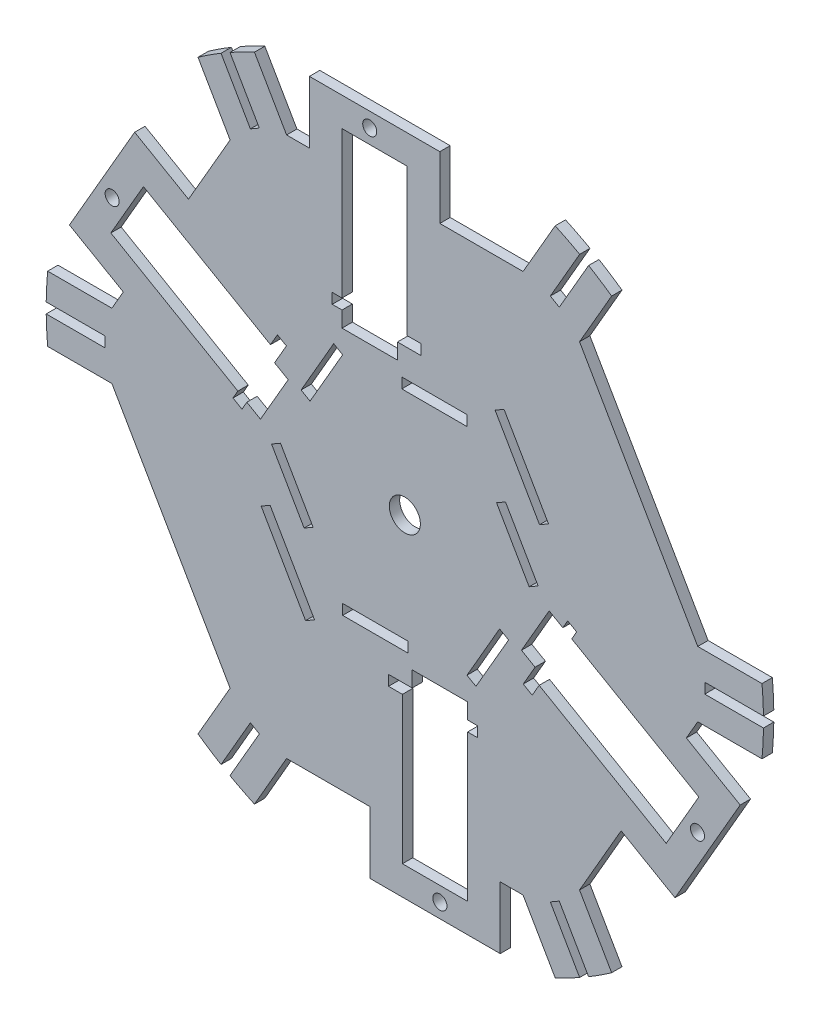
SolidWorks part; units mm, degrees
note: '?' marks a value the reader was unsure of.
ref_plane "Front Plane" through (0, 0, 0) normal (0, 0, 1) x (1, 0, 0)
ref_plane "Top Plane" through (0, 0, 0) normal (0, 1, 0) x (1, 0, 0)
ref_plane "Right Plane" through (0, 0, 0) normal (1, 0, 0) x (0, 0, -1)
sketch "Sketch1" plane through (0, 0, 0) normal (0, 0, 1) x (1, 0, 0)
  line L0 (-4.7625, 0) -> (-4.7625, 42.8001) construction
  line L1 (-4.7625, 40) -> (-2.2625, 40)
  line L2 (-2.2625, 40) -> (-2.2625, 48)
  line L3 (-2.2625, 48) -> (0.7375, 48)
  line L4 (0.7375, 48) -> (0.7375, 93)
  line L5 (0.7375, 93) -> (-19.2625, 93)
  line L6 (-19.2625, 93) -> (-19.2625, 40)
  line L7 (-19.2625, 40) -> (-16.7625, 40)
  line L8 (-16.7625, 40) -> (-4.7625, 40)
  line L9 (-4.7625, 40) -> (-4.7625, 0)
  line L10 (4.7625, -40) -> (2.2625, -40)
  line L11 (2.2625, -40) -> (2.2625, -48)
  line L12 (2.2625, -48) -> (-0.7375, -48)
  line L13 (-0.7375, -48) -> (-0.7375, -93)
  line L14 (-0.7375, -93) -> (19.2625, -93)
  line L15 (19.2625, -93) -> (19.2625, -40)
  line L16 (19.2625, -40) -> (16.7625, -40)
  line L17 (16.7625, -40) -> (4.7625, -40)
  line L18 (-2.2625, 40) -> (2.2625, -40) construction
  line L19 (37.0223, -15.8756) -> (35.7723, -18.0406)
  line L20 (35.7723, -18.0406) -> (42.7005, -22.0406)
  line L21 (42.7005, -22.0406) -> (41.2005, -24.6387)
  line L22 (41.2005, -24.6387) -> (80.1716, -47.1387)
  line L23 (80.1716, -47.1387) -> (90.1716, -29.8182)
  line L24 (90.1716, -29.8182) -> (44.2723, -3.3182)
  line L25 (44.2723, -3.3182) -> (43.0223, -5.4832)
  line L26 (43.0223, -5.4832) -> (37.0223, -15.8756)
  line L27 (0, 0) -> (2.2625, -40) construction
  line L28 (0, 0) -> (35.7723, -18.0406) construction
  line L29 (-37.0223, 15.8756) -> (-35.7723, 18.0406)
  line L30 (-35.7723, 18.0406) -> (-42.7005, 22.0406)
  line L31 (-42.7005, 22.0406) -> (-41.2005, 24.6387)
  line L32 (-41.2005, 24.6387) -> (-80.1716, 47.1387)
  line L33 (-80.1716, 47.1387) -> (-90.1716, 29.8182)
  line L34 (-90.1716, 29.8182) -> (-44.2723, 3.3182)
  line L35 (-44.2723, 3.3182) -> (-43.0223, 5.4832)
  line L36 (-43.0223, 5.4832) -> (-37.0223, 15.8756)
  line L37 (-35.7723, 18.0406) -> (0, 0) construction
  circle A0 centre (0, 0) radius 110
  circle A1 centre (0, 0) radius 4.7625
  point P14 (-4.7625, 0)
  point P27 (0, 0)
  point P46 (0, 0)
  dimension "D5" = 9.525
  dimension "D11" = 220
  dimension "D1" = 17
  dimension "D2" = 12
  dimension "D3" = 53
  dimension "D4" = 45
  dimension "D6" = 20
  dimension "D7" = 40
  dimension "D10" = 60
  dimension "D8" = 2
  dimension "D9" = 2
  dimension "D12" = 2
extrude "Boss-Extrude1" add sketch "Sketch1" along normal mid plane 3.175
sketch "Sketch2" plane through (0, 0, 1.5875) normal (0, 0, 1) x (1, 0, 0)
  line L0 (-0.7375, -93) -> (19.2625, -93) construction
  line L1 (-10.7375, -82.8085) -> (-10.7375, -101.88)
  line L2 (0, 0) -> (45.6639, 0) construction
  line L3 (29.2625, -101.88) -> (29.2625, -82.8085)
  line L4 (-36.2625, -82.8085) -> (-10.7375, -82.8085)
  line L5 (-10.7375, -101.88) -> (9.2625, -101.88)
  line L6 (10.7625, -99.5925) -> (10.7625, -101.88) construction
  line L7 (9.2625, -101.88) -> (29.2625, -101.88)
  line L8 (29.2625, -82.8085) -> (36.2625, -82.8085)
  line L9 (9.2625, -93) -> (9.2625, -101.88) construction
  line L11 (10.7625, -40) -> (10.7625, -97.4387) construction
  line L12 (0, -53.2538) -> (0, -302.3208) construction
  line L13 (0, -55) -> (0, 55) construction
  line L14 (0, 0) -> (55, -95.2628) construction
  line L15 (0, 0) -> (-55, -95.2628) construction
  line L16 (19.2625, -40) -> (2.2625, -40) construction
  line L19 (-36.2625, -82.8085) -> (-46.112, -99.8683)
  line L24 (36.2625, -82.8085) -> (46.112, -99.8683)
  arc A0 (-46.112, -99.8683) -> (46.112, -99.8683) centre (0, 0) ccw
  circle A1 centre (0, 0) radius 110 construction
  circle A2 centre (0, 0) radius 110 construction
  circle A3 centre (10.7625, -97.4387) radius 2.1538
  point P4 (10.7625, -95.285)
  dimension "D10" = 4.3075
  dimension "D2" = 2.2875
  dimension "D3" = 60
  dimension "D4" = 10
  dimension "D5" = 7
  dimension "D6" = 2.285
  dimension "D7" = 20
  dimension "D9" = 10
extrude "Cut-Extrude3" cut sketch "Sketch2" against normal through all
ref_axis "Axis1" through (0, 0, 1.7463) along (0, 0, -1)?
pattern_circular "CirPattern1" count 2 over 360 about axis through (0, 0, 0) along (0, 0, 1) of "Cut-Extrude3"
pattern_circular "CirPattern2" count 2 every 60 about axis through (0, 0, 0) along (0, 0, 1) of "CirPattern1", "Cut-Extrude3"
sketch "Sketch5" plane through (0, 0, 1.5875) normal (0, 0, 1) x (1, 0, 0)
  line L0 (0, 0) -> (-174.8424, -100.9453) construction
  line L1 (0, 0) -> (-55, -95.2628) construction
  line L2 (0, 0) -> (-151.9227, 0) construction
  line L3 (89.8455, 10) -> (53.583, 72.8085)
  line L4 (63.4325, 89.8683) -> (53.583, 72.8085)
  line L5 (-89.8455, -10) -> (-53.583, -72.8085)
  line L6 (-36.2625, -82.8085) -> (-46.112, -99.8683) construction
  line L7 (109.5445, 10) -> (89.8455, 10)
  line L9 (-109.5445, 10) -> (-89.8455, 10) construction
  line L12 (-63.4325, -89.8683) -> (-53.583, -72.8085)
  line L13 (-109.5445, -10) -> (-89.8455, -10)
  arc A0 (-109.5445, -10) -> (-63.4325, -89.8683) centre (0, 0) ccw
  arc A1 (-109.5445, 10) -> (-46.112, -99.8683) centre (0, 0) ccw construction
  arc A2 (109.5445, 10) -> (63.4325, 89.8683) centre (0, 0) ccw
  point P19 (0, 0)
  point P23 (0, 0)
  point P26 (0, 0)
  dimension "D1" = 10
  dimension "D2" = 2
extrude "Cut-Extrude5" cut sketch "Sketch5" against normal through all
sketch "Sketch10" plane through (0, 0, 1.5875) normal (0, 0, 1) x (1, 0, 0)
  line L0 (-55.0026, -95.2673) -> (-50.5318, -87.5237) construction
  line L1 (-65.3691, -110.0476) -> (-56.3691, -94.4591)
  line L2 (-56.3691, -94.4591) -> (-47.3691, -78.8707)
  line L3 (-47.3691, -78.8707) -> (-44.6195, -80.4582)
  line L4 (-44.6195, -80.4582) -> (-53.6195, -96.0466)
  line L5 (-53.6195, -96.0466) -> (-62.6195, -111.6351)
  line L6 (-62.6195, -111.6351) -> (-65.3691, -110.0476)
  line L7 (-53.583, -72.8085) -> (-36.2625, -82.8085) construction
  line L8 (-89.8455, 10) -> (-89.8455, -10) construction
  line L9 (-127.9885, 1.5875) -> (-109.9885, 1.5875)
  line L10 (-109.9885, 1.5875) -> (-91.9885, 1.5875)
  line L11 (-91.9885, 1.5875) -> (-91.9885, -1.5875)
  line L12 (-91.9885, -1.5875) -> (-109.9885, -1.5875)
  line L13 (-109.9885, -1.5875) -> (-127.9885, -1.5875)
  line L14 (-127.9885, -1.5875) -> (-127.9885, 1.5875)
  line L15 (-36.2625, 82.8085) -> (-53.583, 72.8085) construction
  line L16 (-62.6195, 111.6351) -> (-53.6195, 96.0466)
  line L17 (-53.6195, 96.0466) -> (-44.6195, 80.4582)
  line L18 (-44.6195, 80.4582) -> (-47.3691, 78.8707)
  line L19 (-47.3691, 78.8707) -> (-56.3691, 94.4591)
  line L20 (-56.3691, 94.4591) -> (-65.3691, 110.0476)
  line L21 (-65.3691, 110.0476) -> (-62.6195, 111.6351)
  line L22 (53.583, 72.8085) -> (36.2625, 82.8085) construction
  line L23 (65.3691, 110.0476) -> (56.3691, 94.4591)
  line L24 (56.3691, 94.4591) -> (47.3691, 78.8707)
  line L25 (47.3691, 78.8707) -> (44.6195, 80.4582)
  line L26 (44.6195, 80.4582) -> (53.6195, 96.0466)
  line L27 (53.6195, 96.0466) -> (62.6195, 111.6351)
  line L28 (62.6195, 111.6351) -> (65.3691, 110.0476)
  line L29 (89.8455, -10) -> (89.8455, 10) construction
  line L30 (127.9885, -1.5875) -> (109.9885, -1.5875)
  line L31 (109.9885, -1.5875) -> (91.9885, -1.5875)
  line L32 (91.9885, -1.5875) -> (91.9885, 1.5875)
  line L33 (91.9885, 1.5875) -> (109.9885, 1.5875)
  line L34 (109.9885, 1.5875) -> (127.9885, 1.5875)
  line L35 (127.9885, 1.5875) -> (127.9885, -1.5875)
  line L36 (36.2625, -82.8085) -> (53.583, -72.8085) construction
  line L37 (62.6195, -111.6351) -> (53.6195, -96.0466)
  line L38 (53.6195, -96.0466) -> (44.6195, -80.4582)
  line L39 (44.6195, -80.4582) -> (47.3691, -78.8707)
  line L40 (47.3691, -78.8707) -> (56.3691, -94.4591)
  line L41 (56.3691, -94.4591) -> (65.3691, -110.0476)
  line L42 (65.3691, -110.0476) -> (62.6195, -111.6351)
  arc A1 (-63.4325, -89.8683) -> (-46.112, -99.8683) centre (0, 0) ccw construction
  point P15 (-45.9943, -79.6644)
  point P16 (-44.9228, -77.8085)
  point P60 (0, 0)
  dimension "D1" = 3.175
  dimension "D2" = 18
extrude "Cut-Extrude8" cut sketch "Sketch10" against normal mid plane 10
sketch "Sketch11" plane through (0, 0, 1.5875) normal (0, 0, 1) x (1, 0, 0)
  line L0 (-19.2625, 40) -> (-2.2625, 40) construction
  line L1 (-19.067, 33.025) -> (-38.134, 0) construction
  line L2 (-38.134, 0) -> (-19.067, -33.025) construction
  line L3 (-19.067, -33.025) -> (19.067, -33.025) construction
  line L4 (19.067, -33.025) -> (38.134, 0) construction
  line L5 (38.134, 0) -> (19.067, 33.025) construction
  line L6 (19.067, 33.025) -> (-19.067, 33.025) construction
  line L7 (-5, -48) -> (22.2625, -48)
  line L9 (-5, -48) -> (-5, -44.825)
  line L10 (-5, -44.825) -> (22.2625, -44.825)
  line L11 (22.2625, -44.825) -> (22.2625, -48)
  line L12 (2.2625, -48) -> (-0.7375, -48) construction
  line L13 (-44.0692, -19.6699) -> (-30.438, -43.2799)
  line L14 (0, -1.7463) -> (0, 1.7463) construction
  line L15 (19.2625, -93) -> (19.2625, -40) construction
  line L16 (-19.067, -33.025) -> (-19.067, -36.2)
  line L17 (-19.067, -36.2) -> (0.933, -36.2)
  line L18 (0.933, -36.2) -> (0.933, -33.025)
  line L20 (-19.067, -33.025) -> (0.933, -33.025)
  line L21 (-44.0692, -19.6699) -> (-41.3196, -18.0824)
  line L22 (-41.3196, -18.0824) -> (-27.6883, -41.6924)
  line L23 (-27.6883, -41.6924) -> (-30.438, -43.2799)
  line L24 (-38.134, 0) -> (-40.8836, -1.5875)
  line L25 (-40.8836, -1.5875) -> (-30.8836, -18.908)
  line L26 (-30.8836, -18.908) -> (-28.134, -17.3205)
  line L27 (-38.134, 0) -> (-28.134, -17.3205)
  line L28 (-38.134, 0) -> (-19.067, -33.025) construction
  line L29 (-39.0692, 28.3301) -> (-52.7005, 4.7201)
  line L30 (-39.0692, 28.3301) -> (-36.3196, 26.7426)
  line L31 (-36.3196, 26.7426) -> (-49.9508, 3.1326)
  line L32 (-49.9508, 3.1326) -> (-52.7005, 4.7201)
  line L33 (-19.067, 33.025) -> (-21.8166, 34.6125)
  line L34 (-21.8166, 34.6125) -> (-31.8166, 17.292)
  line L35 (-31.8166, 17.292) -> (-29.067, 15.7045)
  line L36 (-19.067, 33.025) -> (-29.067, 15.7045)
  line L37 (-19.067, 33.025) -> (-38.134, 0) construction
  line L38 (5, 48) -> (-22.2625, 48)
  line L39 (5, 48) -> (5, 44.825)
  line L40 (5, 44.825) -> (-22.2625, 44.825)
  line L41 (-22.2625, 44.825) -> (-22.2625, 48)
  line L42 (19.067, 33.025) -> (19.067, 36.2)
  line L43 (19.067, 36.2) -> (-0.933, 36.2)
  line L44 (-0.933, 36.2) -> (-0.933, 33.025)
  line L45 (19.067, 33.025) -> (-0.933, 33.025)
  line L46 (19.067, 33.025) -> (-19.067, 33.025) construction
  line L47 (44.0692, 19.6699) -> (30.438, 43.2799)
  line L48 (44.0692, 19.6699) -> (41.3196, 18.0824)
  line L49 (41.3196, 18.0824) -> (27.6883, 41.6924)
  line L50 (27.6883, 41.6924) -> (30.438, 43.2799)
  line L51 (38.134, 0) -> (40.8836, 1.5875)
  line L52 (40.8836, 1.5875) -> (30.8836, 18.908)
  line L53 (30.8836, 18.908) -> (28.134, 17.3205)
  line L54 (38.134, 0) -> (28.134, 17.3205)
  line L55 (38.134, 0) -> (19.067, 33.025) construction
  line L56 (39.0692, -28.3301) -> (52.7005, -4.7201)
  line L57 (39.0692, -28.3301) -> (36.3196, -26.7426)
  line L58 (36.3196, -26.7426) -> (49.9508, -3.1326)
  line L59 (49.9508, -3.1326) -> (52.7005, -4.7201)
  line L60 (19.067, -33.025) -> (21.8166, -34.6125)
  line L61 (21.8166, -34.6125) -> (31.8166, -17.292)
  line L62 (31.8166, -17.292) -> (29.067, -15.7045)
  line L63 (19.067, -33.025) -> (29.067, -15.7045)
  line L64 (19.067, -33.025) -> (38.134, 0) construction
  circle A0 centre (0, 0) radius 33.025 construction
  point P72 (0, 0)
  dimension "D1" = 66.05
  dimension "D2" = 5
  dimension "D3" = 3
  dimension "D4" = 3.175
  dimension "D5" = 3.175
  dimension "D6" = 20
  dimension "D7" = 6
extrude "Cut-Extrude24" cut sketch "Sketch11" against normal mid plane 10
ref_plane "Plane2" through (0, 0, 0) normal (0.8912, 0.4537, 0) x (0, 0, -1)
